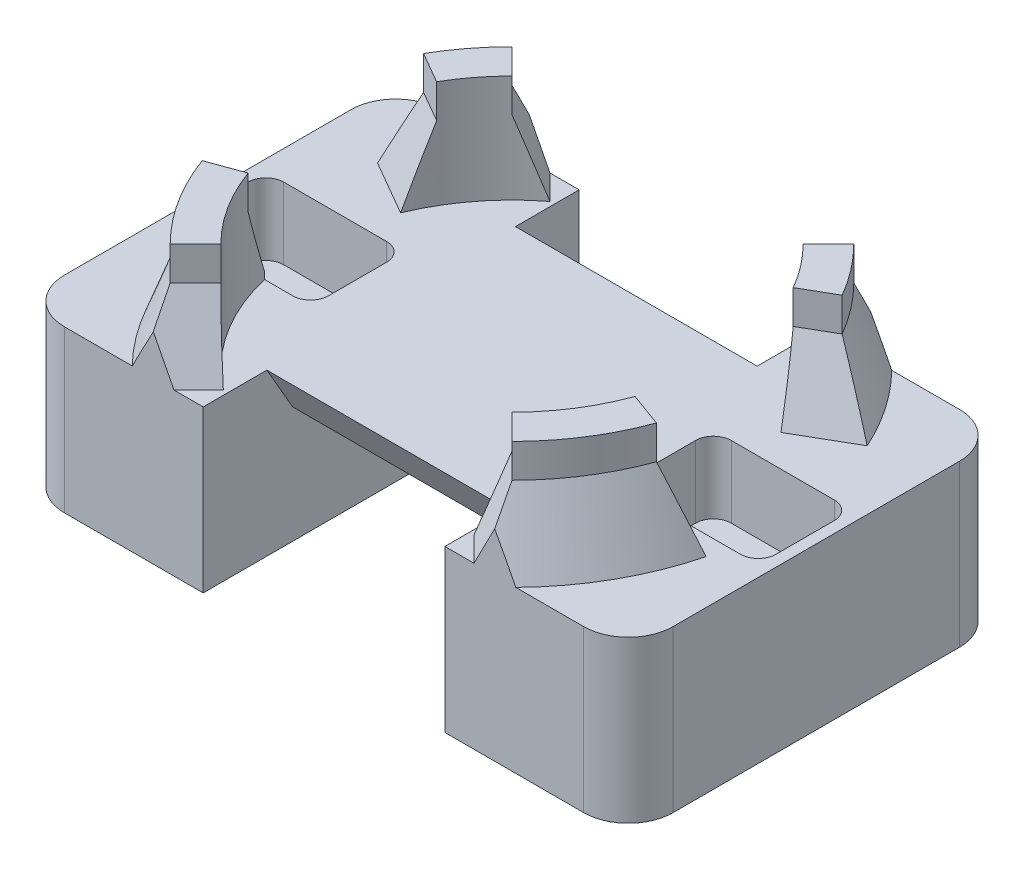
SolidWorks part; units mm, degrees
material "PUR"
ref_plane "Front Plane" through (0, 0, 0) normal (0, 0, 1) x (1, 0, 0)
ref_plane "Top Plane" through (0, 0, 0) normal (0, 1, 0) x (1, 0, 0)
ref_plane "Right Plane" through (0, 0, 0) normal (1, 0, 0) x (0, 0, -1)
sketch "Sketch1" plane through (0, 0, 0) normal (0, 1, 0) x (1, 0, 0)
  line L5 (-13.5, 0) -> (13.5, 0) construction
  line L24 (-18.5, 21) -> (-29, 21)
  line L60 (-34, 16) -> (-34, -16)
  line L61 (-29, -21) -> (-18.5, -21)
  line L62 (18.5, 21) -> (29, 21)
  line L63 (34, 16) -> (34, -16)
  line L64 (29, -21) -> (18.5, -21)
  line L65 (-18.5, 21) -> (-13.5, 21)
  line L66 (-13.5, 21) -> (-13.5, 16)
  line L67 (18.5, 21) -> (13.5, 21)
  line L68 (13.5, 21) -> (13.5, 16)
  line L69 (13.5, -16) -> (13.5, -21)
  line L70 (13.5, -21) -> (18.5, -21)
  line L71 (-13.5, -16) -> (-13.5, -21)
  line L72 (-13.5, -21) -> (-18.5, -21)
  line L73 (-13.5, -16) -> (-13.5, 16)
  line L74 (13.5, -16) -> (13.5, 16)
  arc A4 (34, -16) -> (29, -21) centre (29, -16) cw
  arc A5 (29, 21) -> (34, 16) centre (29, 16) cw
  arc A9 (-29, 21) -> (-34, 16) centre (-29, 16) ccw
  arc A11 (-34, -16) -> (-29, -21) centre (-29, -16) ccw
  point P3 (0, 0)
  point P7 (-13.5, 0)
  point P10 (13.5, 0)
  point P23 (-13.5, 21)
  point P26 (-34, 21)
  point P31 (-34, -21)
  point P35 (-13.5, 0)
  point P36 (13.5, 0)
  dimension "D3" = 20.5
  dimension "D4" = 5
  dimension "D1" = 27
  dimension "D2" = 42
  dimension "D5" = 5
  dimension "D6" = 5
extrude "Boss-Extrude1" add sketch "Sketch1" against normal blind 3 and the other way blind 15
sketch "Sketch2" plane through (0, 15, 0) normal (0, 1, 0) x (1, 0, 0)
  line L0 (-13.5, 16) -> (13.5, 16)
  line L1 (13.5, 16) -> (13.5, -16)
  line L2 (13.5, -16) -> (-13.5, -16)
  line L3 (-13.5, -16) -> (-13.5, 16)
  line L4 (-13.5, -21) -> (-13.5, 21) construction
  line L7 (13.5, 21) -> (13.5, -21) construction
  line L8 (-13.5, 21) -> (-29, 21) construction
  line L9 (-29, -21) -> (-13.5, -21) construction
  dimension "D1" = 5
  dimension "D2" = 5
extrude "Boss-Extrude2" add sketch "Sketch2" against normal blind 5
chamfer "Chamfer1" distance 5 angle 60 2 edges at (0, 10, -16) (0, 10, 16) first distance on face at (0, 10, 0)
sketch "Sketch3" plane through (0, 15, 0) normal (0, 1, 0) x (1, 0, 0)
  line L0 (-25, 0) -> (25, 0) construction
  line L1 (0, -16) -> (0, 16) construction
  line L2 (-30.75, -5.25) -> (-19.25, -5.25)
  line L3 (-32.75, -3.25) -> (-32.75, 3.25)
  line L4 (-30.75, 5.25) -> (-19.25, 5.25)
  line L5 (-17.25, -3.25) -> (-17.25, 3.25)
  line L6 (-32.75, -5.25) -> (-17.25, 5.25) construction
  line L7 (-32.75, 5.25) -> (-17.25, -5.25) construction
  line L9 (30.75, 5.25) -> (19.25, 5.25)
  line L10 (17.25, -3.25) -> (17.25, 3.25)
  line L11 (30.75, -5.25) -> (19.25, -5.25)
  line L12 (32.75, -3.25) -> (32.75, 3.25)
  arc A0 (-17.25, 3.25) -> (-19.25, 5.25) centre (-19.25, 3.25) ccw
  arc A1 (-19.25, -5.25) -> (-17.25, -3.25) centre (-19.25, -3.25) ccw
  arc A2 (-32.75, -3.25) -> (-30.75, -5.25) centre (-30.75, -3.25) ccw
  arc A3 (-32.75, 3.25) -> (-30.75, 5.25) centre (-30.75, 3.25) cw
  arc A4 (17.25, 3.25) -> (19.25, 5.25) centre (19.25, 3.25) cw
  arc A5 (19.25, -5.25) -> (17.25, -3.25) centre (19.25, -3.25) cw
  arc A6 (32.75, -3.25) -> (30.75, -5.25) centre (30.75, -3.25) cw
  arc A7 (32.75, 3.25) -> (30.75, 5.25) centre (30.75, 3.25) ccw
  point P4 (0, 0)
  point P14 (0, 0)
  point P37 (0, 0)
  dimension "D4" = 2
  dimension "D1" = 50
  dimension "D2" = 10.5
  dimension "D3" = 15.5
extrude "Cut-Extrude1" cut sketch "Sketch3" against normal blind 8
sketch "Sketch4" plane through (0, 15, 0) normal (0, 1, 0) x (1, 0, 0)
  line L0 (0, 0) -> (-23.3827, 13.5) construction
  line L1 (0, 0) -> (-19.0919, 19.0919) construction
  line L2 (0, -27) -> (0, 27) construction
  line L3 (0, 0) -> (-25.3717, -9.2345) construction
  line L4 (0, 0) -> (-19.0919, -19.0919) construction
  line L5 (-23.3827, 13.5) -> (-19.9186, 11.5)
  line L6 (-19.0919, 19.0919) -> (-16.2635, 16.2635)
  line L7 (-19.0919, -19.0919) -> (-16.2635, -16.2635)
  line L8 (-21.6129, -7.8665) -> (-25.3717, -9.2345)
  line L9 (23.3827, 13.5) -> (19.9186, 11.5)
  line L10 (19.0919, 19.0919) -> (16.2635, 16.2635)
  line L11 (19.0919, -19.0919) -> (16.2635, -16.2635)
  line L12 (21.6129, -7.8665) -> (25.3717, -9.2345)
  circle A0 centre (0, 0) radius 23 construction
  circle A1 centre (0, 0) radius 27 construction
  arc A2 (-25.3717, -9.2345) -> (-19.0919, -19.0919) centre (0, 0) ccw
  arc A3 (-21.6129, -7.8665) -> (-16.2635, -16.2635) centre (0, 0) ccw
  arc A4 (-19.9186, 11.5) -> (-16.2635, 16.2635) centre (0, 0) cw
  arc A5 (-19.0919, 19.0919) -> (-23.3827, 13.5) centre (0, 0) ccw
  arc A6 (19.0919, 19.0919) -> (23.3827, 13.5) centre (0, 0) cw
  arc A7 (19.9186, 11.5) -> (16.2635, 16.2635) centre (0, 0) ccw
  arc A8 (25.3717, -9.2345) -> (19.0919, -19.0919) centre (0, 0) cw
  arc A9 (21.6129, -7.8665) -> (16.2635, -16.2635) centre (0, 0) cw
  point P9 (0, 0)
  dimension "D1" = 4
  dimension "D2" = 46
  dimension "D3" = 15
  dimension "D4" = 45
  dimension "D5" = 25
  dimension "D6" = 45
extrude "Boss-Extrude3" add sketch "Sketch4" along normal blind 12 contours L6 A5 L5 A4 | A3 L8 A2 L7 | A7 L9 A6 L10 | L12 A9 L11 A8 region at (-19.8194, 15, -15.208) region at (-20.9625, 15, 13.3546) region at (19.8194, 15, -15.208) region at (20.9625, 15, 13.3546)
chamfer "Chamfer2" distance 3 angle 70 12 edges at (17.6777, 15, -17.6777) (21.4205, 15, -16.4366) (21.6506, 15, -12.5) (-21.6506, 15, -12.5) (-17.6777, 15, -17.6777) (-21.4205, 15, -16.4366) (23.4923, 15, 8.5505) (22.7716, 15, 14.5071) (17.6777, 15, 17.6777) (-23.4923, 15, 8.5505) (-17.6777, 15, 17.6777) (-22.7716, 15, 14.5071) first distance on face at (20.8349, 15, 13.2733)
sketch "Sketch5" plane through (0, 7, 0) normal (0, 1, 0) x (1, 0, 0)
  line L0 (-23, 0) -> (23, 0)
  circle A0 centre (-23, 0) radius 1.8
  circle A1 centre (23, 0) radius 1.8
  point P4 (0, 0)
  dimension "D2" = 3.6
  dimension "D1" = 46
extrude "Cut-Extrude2" cut sketch "Sketch5" against normal blind 10 contours A0 | A1 region at (23, 7, -1.7491) region at (-24.7491, 7, 0)
